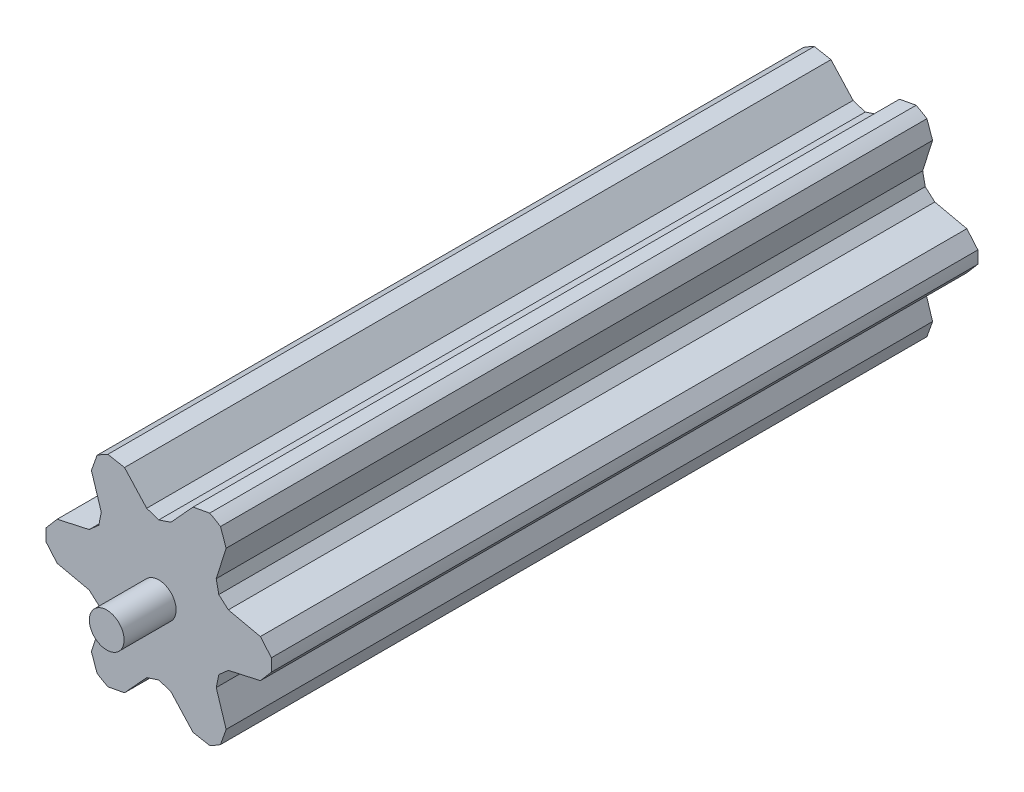
SolidWorks part; units mm, degrees
ref_plane "Front Plane" through (0, 0, 0) normal (0, 0, 1) x (1, 0, 0)
ref_plane "Top Plane" through (0, 0, 0) normal (0, 1, 0) x (1, 0, 0)
ref_plane "Right Plane" through (0, 0, 0) normal (1, 0, 0) x (0, 0, -1)
sketch "Sketch1" plane through (0, 0, 0) normal (0, 0, 1) x (1, 0, 0)
  line L1 (1.2374, -1.2374) -> (-1.2374, -1.2374) construction
  line L2 (1.2374, -1.2374) -> (1.2374, 1.2374) construction
  line L3 (1.2374, 1.2374) -> (-1.2374, 1.2374) construction
  line L4 (-1.2374, -1.2374) -> (-1.2374, 1.2374) construction
  line L5 (1.2374, -1.2374) -> (-1.2374, 1.2374) construction
  line L6 (1.2374, 1.2374) -> (-1.2374, -1.2374) construction
  circle A0 centre (0, 0) radius 6.5
  circle A1 centre (0, 0) radius 1.75 construction
  dimension "D1" = 13
  dimension "D2" = 3.5
extrude "Boss-Extrude1" add sketch "Sketch1" along normal blind 40.71
sketch "Sketch2" plane through (0, 0, 0) normal (0, 0, 1) x (1, 0, 0)
  line L0 (0, 0) -> (0, 10.088) construction
  line L1 (0, 3.994) -> (-0.6978, 4.226)
  line L8 (-3.4668, 8.7118) -> (0, 10.6127)
  line L11 (-0.6978, 4.226) -> (-1.9741, 5.6218)
  line L12 (-1.9741, 5.6218) -> (-2.934, 5.8001)
  line L13 (-2.934, 5.8001) -> (-3.4668, 8.7118)
  line L14 (2.934, 5.8001) -> (3.4668, 8.7118)
  line L15 (1.9741, 5.6218) -> (2.934, 5.8001)
  line L16 (0.6978, 4.226) -> (1.9741, 5.6218)
  line L17 (3.4668, 8.7118) -> (0, 10.6127)
  line L18 (0, 3.994) -> (0.6978, 4.226)
  circle A14 centre (0, 0) radius 6.5 construction
  point P4 (0, 3.994)
  point P16 (0, 6.5)
  point P17 (-1.4007, 4.9784)
  point P18 (-2.2581, 6.4762)
  point P19 (-2.522, 6.4621)
  point P20 (-0.6978, 4.226)
  point P21 (-1.7159, 5.9542)
  point P22 (-2.8653, 6.9311)
  point P23 (-3.4668, 8.7118)
  point P24 (0, 10.6127)
  point P25 (-2.934, 5.8001)
  point P26 (-1.9741, 5.6218)
extrude "Cut-Extrude1" cut sketch "Sketch2" along normal through all
pattern_circular "CirPattern1" count 6 over 360 about axis through (0, 0, 40.71) along (0, 0, -1) of "Cut-Extrude1" reverse direction yes
sketch "Sketch3" plane through (0, 0, 0) normal (0, 0, 1) x (1, 0, 0)
  circle A0 centre (0, 0) radius 7.5
  dimension "D1" = 15
sketch "Sketch4" plane through (0, 0, 40.71) normal (0, 0, 1) x (1, 0, 0)
  circle A0 centre (0, 0) radius 1
  dimension "D1" = 2
extrude "Boss-Extrude2" add sketch "Sketch4" along normal blind 3
